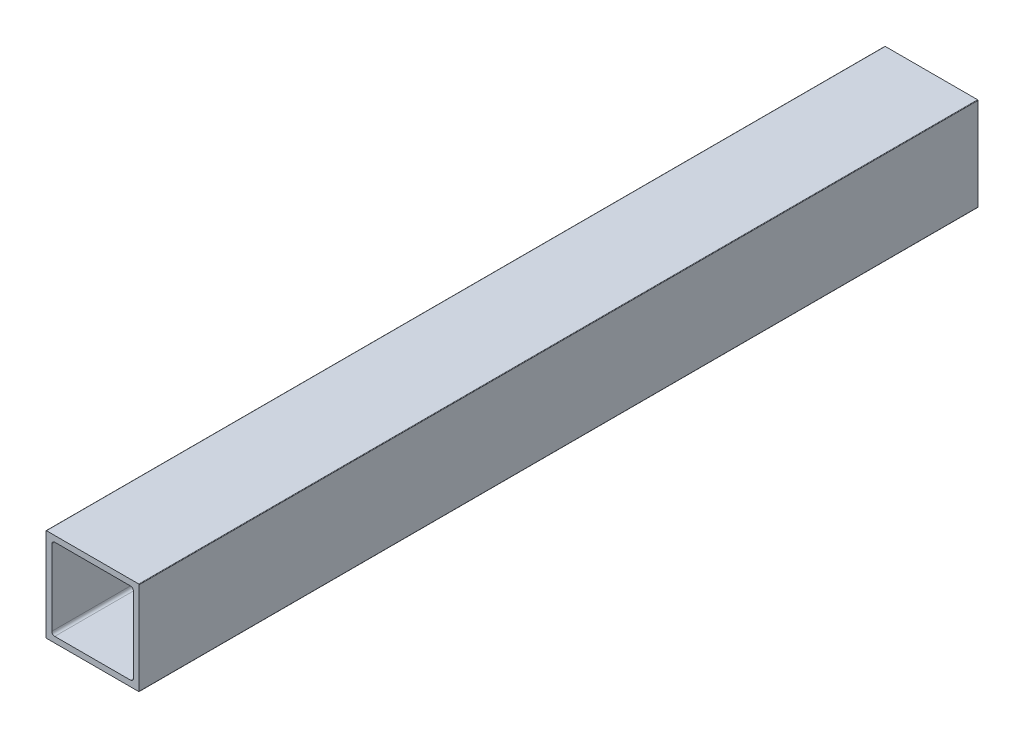
SolidWorks part; units mm, degrees
ref_plane "Front Plane" through (0, 0, 0) normal (0, 0, 1) x (1, 0, 0)
ref_plane "Top Plane" through (0, 0, 0) normal (0, 1, 0) x (1, 0, 0)
ref_plane "Right Plane" through (0, 0, 0) normal (1, 0, 0) x (0, 0, -1)
ref_plane "Plane1" through (0, 0, 0) normal (0, 0, -1) x (-1, 0, 0)
sketch "Sketch1" plane through (0, 0, 0) normal (0, 0, -1) x (-1, 0, 0)
  line L0 (22.225, 46.0375) -> (22.225, 4.7625)
  line L1 (20.6375, 3.175) -> (-20.6375, 3.175)
  line L2 (-22.225, 4.7625) -> (-22.225, 46.0375)
  line L3 (-20.6375, 47.625) -> (20.6375, 47.625)
  line L4 (25.4, 0.254) -> (25.4, 50.546)
  line L5 (25.146, 50.8) -> (-25.146, 50.8)
  line L6 (-25.4, 50.546) -> (-25.4, 0.254)
  line L7 (-25.146, 0) -> (25.146, 0)
  arc A0 (22.225, 4.7625) -> (20.6375, 3.175) centre (20.6375, 4.7625) cw
  arc A1 (-20.6375, 3.175) -> (-22.225, 4.7625) centre (-20.6375, 4.7625) cw
  arc A2 (-22.225, 46.0375) -> (-20.6375, 47.625) centre (-20.6375, 46.0375) cw
  arc A3 (20.6375, 47.625) -> (22.225, 46.0375) centre (20.6375, 46.0375) cw
  arc A4 (25.146, 0) -> (25.4, 0.254) centre (25.146, 0.254) ccw
  arc A5 (25.4, 50.546) -> (25.146, 50.8) centre (25.146, 50.546) ccw
  arc A6 (-25.146, 50.8) -> (-25.4, 50.546) centre (-25.146, 50.546) ccw
  arc A7 (-25.4, 0.254) -> (-25.146, 0) centre (-25.146, 0.254) ccw
  dimension "D1" = 50.8
  dimension "D2" = 50.8
  dimension "D3" = 44.45
  dimension "D4" = 3.175
  dimension "D5" = 44.45
extrude "Boss-Extrude1" add sketch "Sketch1" against normal blind 457.2
